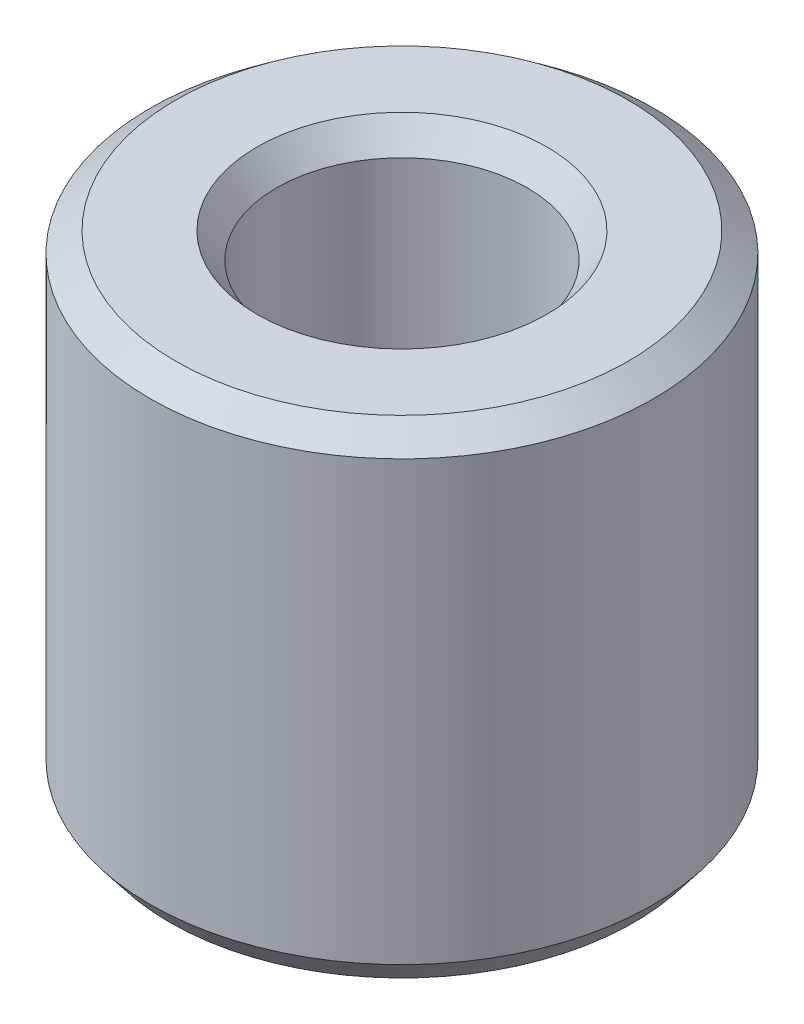
SolidWorks part; units mm, degrees
ref_plane "Front Plane" through (0, 0, 0) normal (0, 0, 1) x (1, 0, 0)
ref_plane "Top Plane" through (0, 0, 0) normal (0, 1, 0) x (1, 0, 0)
ref_plane "Right Plane" through (0, 0, 0) normal (1, 0, 0) x (0, 0, -1)
sketch "Sketch1" plane through (0, 0, 0) normal (0, 1, 0) x (1, 0, 0)
  circle A0 centre (0, 0) radius 35
  dimension "SLEEVE_OD" = 70
extrude "Boss-Extrude1" add sketch "Sketch1" along normal blind 67.1847
sketch "Sketch2" plane through (0, 0, 0) normal (0, 1, 0) x (1, 0, 0)
  circle A0 centre (0, 0) radius 17.4215
  dimension "BORE_D" = 34.8431
extrude "Cut-Extrude1" cut sketch "Sketch2" along normal through all
chamfer "Chamfer1" distance 2.7398 angle 52.288 4 edges at (0, 67.1847, 17.4215) (0, 0, 17.4215) (0, 0, 35) (0, 67.1847, 35) first distance on face at (0, 67.1847, 17.4215) first distance on face at (0, 0, 17.4215) first distance on face at (0, 67.1847, 35)
